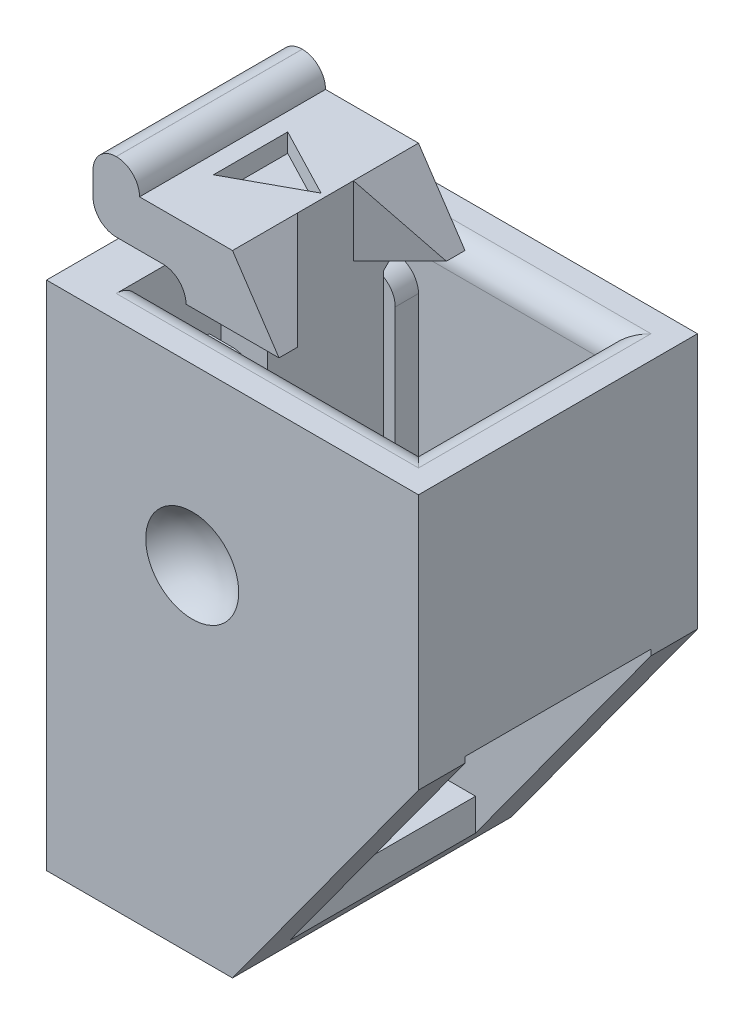
SolidWorks part; units mm, degrees
ref_plane "Front Plane" through (0, 0, 0) normal (0, 0, 1) x (1, 0, 0)
ref_plane "Top Plane" through (0, 0, 0) normal (0, 1, 0) x (1, 0, 0)
ref_plane "Right Plane" through (0, 0, 0) normal (1, 0, 0) x (0, 0, -1)
sketch "BaseSketch" plane through (0, 0, 0) normal (0, 1, 0) x (1, 0, 0)
  line L1 (-6.2677, 3.9685) -> (9.7323, 3.9685)
  line L2 (-6.2677, 3.9685) -> (-6.2677, -8.0315)
  line L3 (-6.2677, -8.0315) -> (9.7323, -8.0315)
  line L4 (9.7323, 3.9685) -> (9.7323, -8.0315)
  dimension "D1" = 16
  dimension "D2" = 12
extrude "BaseExtrude" add sketch "BaseSketch" along normal blind 2
sketch "SlotSketch" plane through (0, 2, 0) normal (0, 1, 0) x (1, 0, 0)
  line L10 (-2.2677, 0.9685) -> (-0.2677, 0.9685)
  line L11 (-2.2677, 1.9685) -> (-4.2677, 1.9685)
  line L12 (-2.2677, 1.9685) -> (-2.2677, 0.9685)
  line L13 (-0.2677, -6.0315) -> (7.7323, -6.0315)
  line L14 (7.7323, -6.0315) -> (7.7323, 1.9685)
  line L15 (-4.2677, -6.0315) -> (7.7323, -6.0315)
  line L16 (-4.2677, 1.9685) -> (-4.2677, -6.0315)
  line L17 (7.7323, 1.9685) -> (-4.2677, 1.9685)
  line L18 (7.7323, -6.0315) -> (7.7323, 1.9685)
  line L19 (-4.2677, -6.0315) -> (-2.2677, -6.0315)
  line L20 (-4.2677, 1.9685) -> (-4.2677, -6.0315)
  line L21 (7.7323, 1.9685) -> (-0.2677, 1.9685)
  line L22 (-0.2677, 1.9685) -> (-0.2677, 0.9685)
  line L23 (-2.2677, -5.0315) -> (-0.2677, -5.0315)
  line L24 (-2.2677, 0.4685) -> (-2.2677, -4.5315)
  line L25 (-2.2677, 0.4685) -> (-0.2677, 0.4685)
  line L26 (-2.2677, 0.4685) -> (-2.2677, -4.5315)
  line L27 (-2.2677, -4.5315) -> (-0.2677, -4.5315)
  line L28 (-0.2677, 0.4685) -> (-0.2677, -4.5315)
  line L29 (-0.2677, 0.4685) -> (-0.2677, -4.5315)
  line L30 (-2.2677, -5.0315) -> (-2.2677, -6.0315)
  line L31 (-0.2677, -5.0315) -> (-0.2677, -6.0315)
  line L33 (-6.2677, 3.9685) -> (9.7323, 3.9685)
  line L34 (-6.2677, 3.9685) -> (-6.2677, -8.0315)
  line L35 (-6.2677, -8.0315) -> (9.7323, -8.0315)
  line L36 (9.7323, 3.9685) -> (9.7323, -8.0315)
  line M5 (-6.2677, 3.9685) -> (-6.2677, -8.0315)
  line M6 (-6.2677, -8.0315) -> (9.7323, -8.0315)
  line M7 (9.7323, -8.0315) -> (9.7323, 3.9685)
  line M8 (9.7323, 3.9685) -> (-6.2677, 3.9685)
  dimension "D2" = 8
  dimension "D3" = 2
  dimension "D4" = 2
  dimension "D5" = 8
  dimension "D6" = 1
  dimension "D7" = 1
  dimension "D8" = 5
  dimension "D9" = 0.5
  dimension "D1" = 2
extrude "FlapExtrude" add sketch "SlotSketch" along normal blind 20.1 contours L25 L28 L27 L24
sketch "HandleBaseSketch" plane through (0, 22.1, 0) normal (0, 1, 0) x (1, 0, 0)
  line L0 (9.7323, 3.9685) -> (-6.2677, 3.9685) construction
  line L1 (-2.2677, 1.9685) -> (-0.2677, 1.9685)
  line L2 (-2.2677, 1.9685) -> (-2.2677, -6.0315)
  line L3 (-2.2677, -6.0315) -> (-0.2677, -6.0315)
  line L4 (-0.2677, 1.9685) -> (-0.2677, -6.0315)
  line L5 (-6.2677, -8.0315) -> (9.7323, -8.0315) construction
  dimension "D1" = 2
  dimension "D2" = 2
extrude "HandleBase" add sketch "HandleBaseSketch" along normal blind 3
sketch "TriangleBaseSketch" plane through (-0.2677, 0, 0) normal (1, 0, 0) x (0, 0, -1)
  line L0 (-6.0315, 22.1) -> (-3.2315, 22.1)
  line L1 (-3.2315, 22.1) -> (-3.2315, 25.1)
  line L2 (-6.0315, 25.1) -> (1.9685, 25.1) construction
  line L3 (-3.2315, 25.1) -> (-6.0315, 25.1)
  line L4 (-6.0315, 25.1) -> (-6.0315, 22.1)
  line L5 (1.9685, 22.1) -> (-0.8315, 22.1)
  line L6 (-0.8315, 22.1) -> (-0.8315, 25.1)
  line L7 (-0.8315, 25.1) -> (1.9685, 25.1)
  line L8 (1.9685, 25.1) -> (1.9685, 22.1)
extrude "PyramidExtrude" add sketch "TriangleBaseSketch" along normal blind 2.8
sketch "PyramidSideCutSketch" plane through (0, 0, -1.9685) normal (0, 0, -1) x (-1, 0, 0)
  line L0 (0.2677, 25.1) -> (0.2677, 22.1)
  line L1 (0.2677, 25.1) -> (-2.5323, 25.1)
  line L2 (-2.5323, 25.1) -> (-2.5323, 22.1)
  line L3 (-2.5323, 22.1) -> (-1.7323, 22.1)
  line L4 (-2.5323, 22.1) -> (2.2677, 22.1) construction
  line L5 (-1.7323, 22.1) -> (0.2677, 25.1)
  dimension "D1" = 2
sketch "PyramidTopCutSketch" plane through (0, 25.1, 0) normal (0, 1, 0) x (1, 0, 0)
  line L0 (-0.2677, -3.2315) -> (2.5323, -6.0315)
  line L1 (2.5323, -6.0315) -> (2.5323, -3.2315)
  line L2 (2.5323, -3.2315) -> (-0.2677, -3.2315)
  line L3 (-0.2677, -0.8315) -> (2.5323, 1.9685)
  line L4 (2.5323, 1.9685) -> (2.5323, -0.8315)
  line L5 (2.5323, -0.8315) -> (-0.2677, -0.8315)
extrude "PyramidTopCut" cut sketch "PyramidTopCutSketch" against normal blind 3
extrude "PyramidSideCut" cut sketch "PyramidSideCutSketch" against normal through all contours L1 L2 L3 L5
extrude "Boss-Extrude5" add sketch "SlotSketch<6>" along normal blind 3 contours L31 L23 L30 L19 L20 L11 L12 L10 L22 L21 L18 L13 M8 M5 M6 M7 | L12 L10 L22 L21 L18 L13 L31 L23 L30 L19 L20 L11 | L33 L36 L35 L34 region at (-1.2677, 2, -1.4685) region at (-1.2677, 2, 5.5315) region at (1.7323, 2, -3.7685)
sketch "SlotSketch<6>" plane through (0, 2, 0) normal (0, 1, 0) x (1, 0, 0) same geometry as "SlotSketch"
extrude "Sides" add sketch "SlotSketch<7>" along normal blind 20 contours L11 L20 L19 L30 L23 L31 L13 L18 L21 L22 L10 L12 | L33 L36 L35 L34
sketch "SlotSketch<7>" plane through (0, 2, 0) normal (0, 1, 0) x (1, 0, 0) same geometry as "SlotSketch"
sketch "Sketch7" plane through (-0.2677, 0, 0) normal (1, 0, 0) x (0, 0, -1)
  line L0 (-5.0315, 22) -> (-5.0315, 2) construction
  line L1 (-6.0315, 22) -> (-5.0315, 22)
  line L2 (-6.0315, 22) -> (-6.0315, 20.4974)
  line L3 (-6.0315, 20.4974) -> (-5.0315, 20.4974)
  line L4 (-5.0315, 22) -> (-5.0315, 20.4974)
  line L5 (1.9685, 22) -> (1.9685, 2) construction
  line L6 (0.9685, 22) -> (1.9685, 22)
  line L7 (0.9685, 22) -> (0.9685, 20.4974)
  line L8 (0.9685, 20.4974) -> (1.9685, 20.4974)
  line L9 (1.9685, 22) -> (1.9685, 20.4974)
extrude "WallClearanceCut" cut sketch "Sketch7" against normal blind 2
sketch "BaseTriangleCutSketch" plane through (0, 0, 8.0315) normal (0, 0, 1) x (1, 0, 0)
  line L0 (9.7323, 0) -> (1.7323, 0)
  line L1 (-6.2677, 0) -> (9.7323, 0) construction
  line L2 (1.7323, 0) -> (9.7323, 11)
  line L3 (9.7323, 22) -> (9.7323, 0) construction
  line L4 (9.7323, 11) -> (9.7323, 0)
extrude "BaseTriangleCut" cut sketch "BaseTriangleCutSketch" against normal through all
sketch "Sketch9" plane through (-2.2677, 0, 0) normal (-1, 0, 0) x (0, 0, 1)
  line L0 (6.0315, 25.1) -> (6.0315, 22.1) construction
  line L1 (-1.9685, 25.1) -> (6.0315, 25.1)
  line L2 (-1.9685, 25.1) -> (-1.9685, 23.1)
  line L3 (-1.9685, 23.1) -> (6.0315, 23.1)
  line L4 (6.0315, 25.1) -> (6.0315, 23.1)
extrude "Handle" add sketch "Sketch9" along normal blind 4
sketch "Sketch10" plane through (0, 25.1, 0) normal (0, 1, 0) x (1, 0, 0)
  line L0 (-0.2677, 1.9685) -> (-6.2677, 1.9685) construction
  line L1 (-6.2677, -6.0315) -> (-4.2659, -6.0315)
  line L2 (-6.2677, -6.0315) -> (-6.2677, 1.9685)
  line L3 (-6.2677, 1.9685) -> (-4.2659, 1.9685)
  line L4 (-4.2659, -6.0315) -> (-4.2659, 1.9685)
extrude "Boss-Extrude8" add sketch "Sketch10" along normal blind 1
sketch "WashHoleSketch" plane through (-6.2677, 0, 0) normal (-1, 0, 0) x (0, 0, 1)
  line L0 (-3.9685, 22) -> (-3.9685, 0) construction
  line L1 (-1.9685, 18) -> (6.0315, 18)
  line L2 (-1.9685, 18) -> (-1.9685, 4)
  line L3 (-1.9685, 4) -> (6.0315, 4)
  line L4 (6.0315, 18) -> (6.0315, 4)
  line L5 (8.0315, 22) -> (8.0315, 0) construction
  line L6 (-3.9685, 22) -> (8.0315, 22) construction
  line L7 (-3.9685, 0) -> (8.0315, 0) construction
  dimension "D1" = 2
  dimension "D2" = 2
  dimension "D3" = 4
  dimension "D4" = 4
extrude "WashHole" cut sketch "WashHoleSketch" against normal blind 2
fillet "Fillet1" radius 1 10 edges at (1.7323, 22, -1.9685) (1.7323, 22, 6.0315) (7.7323, 22, 2.0315) (-2.2677, 2, 2.0315) (-2.2677, 23.1, 2.0315) (-6.2677, 23.1, 2.0315) (-4.2659, 26.1, 2.0315) (-6.2677, 26.1, 2.0315) (-0.2677, 20.4974, -1.4685) (-0.2677, 20.4974, 5.5315)
sketch "MarkerSketch" plane through (0, 25.1, 0) normal (0, 1, 0) x (1, 0, 0)
  line L0 (-0.4994, -1.9893) -> (-3.4984, -0.4264)
  line L1 (-3.4984, -0.4264) -> (-3.4984, -3.6225)
  line L2 (-3.4984, -3.6225) -> (-0.4994, -1.9893)
extrude "Cut-Extrude6" cut sketch "MarkerSketch" against normal blind 0.8
sketch "Sketch11" plane through (7.7323, 0, 0) normal (-1, 0, 0) x (0, 0, 1)
  line L1 (6.0315, 8.25) -> (-1.9685, 8.25)
  line L2 (6.0315, 8.25) -> (6.0315, 11.25)
  line L3 (6.0315, 11.25) -> (-1.9685, 11.25)
  line L4 (-1.9685, 8.25) -> (-1.9685, 11.25)
  dimension "D1" = 3
extrude "Cut-Extrude7" cut sketch "Sketch11" against normal blind 10
sketch "Sketch12" plane through (0, 2, 0) normal (0, 1, 0) x (1, 0, 0)
  line L0 (-0.2677, -6.0315) -> (3.1868, -6.0315) construction
  line L1 (3.1868, 1.9685) -> (2.1868, 1.9685)
  line L2 (3.1868, 1.9685) -> (3.1868, -6.0315)
  line L3 (3.1868, -6.0315) -> (2.1868, -6.0315)
  line L4 (2.1868, 1.9685) -> (2.1868, -6.0315)
  dimension "D1" = 1
extrude "Cut-Extrude8" cut sketch "Sketch12" against normal blind 10
chamfer "Chamfer1" distance 1 angle 45 2 edges
sketch "Sketch16" plane through (0, 0, 0) normal (1, 0, 0) x (0, 0, -1)
  line L0 (-8.0315, 16.5) -> (-8.0315, 14.5)
  line L1 (-8.0315, 22) -> (-8.0315, 11) construction
  line L2 (-8.0315, 14.5) -> (-7.0315, 14.5)
  line L4 (-7.0315, 14.5) -> (-11.385, 14.5) construction
  arc A0 (-7.0315, 14.5) -> (-8.0315, 16.5) centre (-9.5315, 14.5) ccw
revolve "Cut-Revolve2" cut sketch "Sketch16" angle 360 about L4
sketch "Sketch17" plane through (0, 0, 0) normal (1, 0, 0) x (0, 0, -1)
  line L0 (3.9685, 16.5) -> (2.9685, 16.5)
  line L1 (3.9685, 22) -> (3.9685, 11) construction
  line L2 (3.9685, 16.5) -> (3.9685, 14.5)
  line L3 (2.9685, 16.5) -> (7.3997, 16.5) construction
  arc A0 (2.9685, 16.5) -> (3.9685, 14.5) centre (5.4685, 16.5) ccw
revolve "Cut-Revolve3" cut sketch "Sketch17" angle 360 about L3
